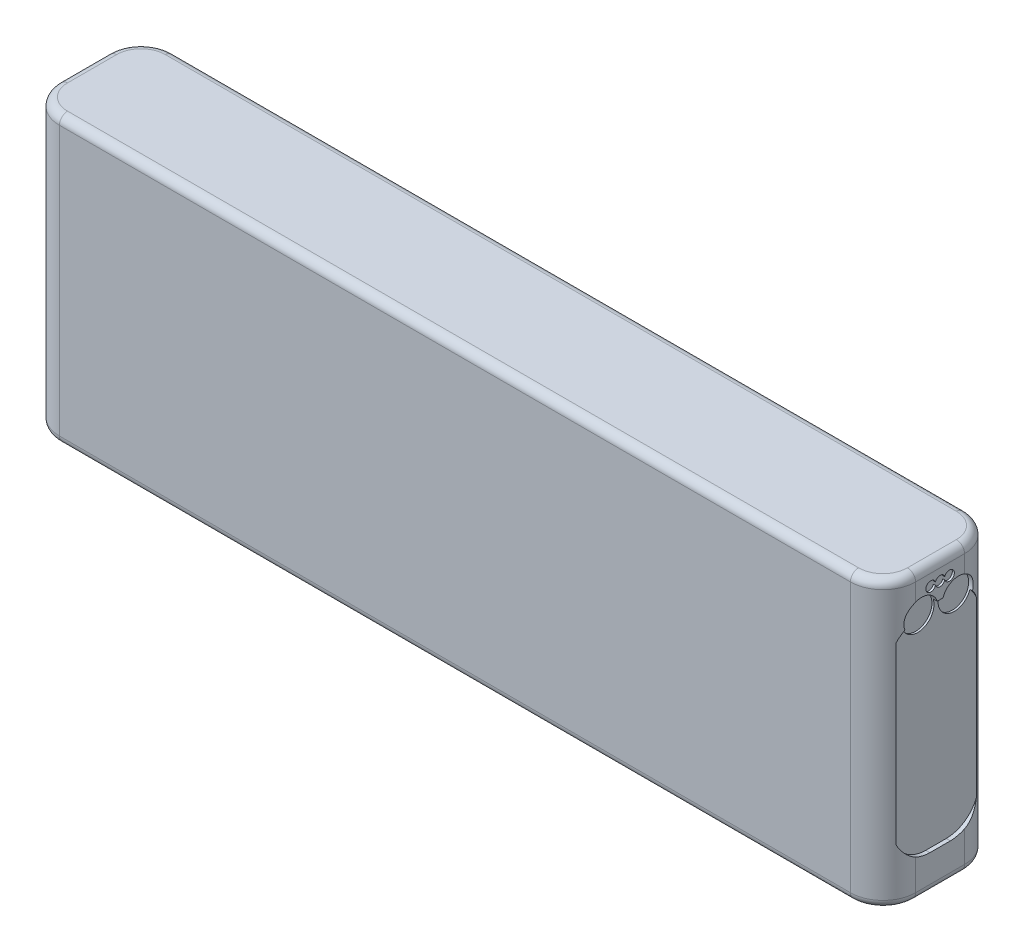
SolidWorks part; units mm, degrees
ref_plane "Front Plane" through (0, 0, 0) normal (0, 0, 1) x (1, 0, 0)
ref_plane "Top Plane" through (0, 0, 0) normal (0, 1, 0) x (1, 0, 0)
ref_plane "Right Plane" through (0, 0, 0) normal (1, 0, 0) x (0, 0, -1)
ref_plane "Plane1" through (0, 0, -15) normal (0, 0, -1) x (-1, 0, 0)
sketch "Sketch1" plane through (0, 0, -15) normal (0, 0, -1) x (-1, 0, 0)
  line L0 (-52.5, -17.5) -> (52.5, -17.5)
  line L1 (52.5, -17.5) -> (52.5, 17.5)
  line L2 (52.5, 17.5) -> (-52.5, 17.5)
  line L3 (-52.5, 17.5) -> (-52.5, -17.5)
  line L4 (-52.5, 0) -> (52.5, 0) construction
  line L5 (0, 17.5) -> (0, -17.5) construction
  dimension "D1" = 35
  dimension "D2" = 105
extrude "Boss-Extrude1" add sketch "Sketch1" against normal blind 14
sketch "Sketch2" plane through (52.5, 0, 0) normal (1, 0, 0) x (0, 0, -1)
  line L0 (2.75, 9.125) -> (2.75, -9.125)
  line L1 (6.75, -13.125) -> (9.25, -13.125)
  line L2 (13.25, -9.125) -> (13.25, 9.125)
  line L3 (9.25, 13.125) -> (6.75, 13.125)
  line L4 (1, 17.5) -> (15, -17.5) construction
  line L5 (15, 17.5) -> (1, -17.5) construction
  line L6 (2.75, 13.125) -> (13.25, -13.125) construction
  line L7 (13.25, 13.125) -> (2.75, -13.125) construction
  line L12 (1, 17.5) -> (15, 17.5) construction
  line L13 (1, 17.5) -> (1, -17.5) construction
  line L14 (1, -17.5) -> (15, -17.5) construction
  line L15 (15, 17.5) -> (15, -17.5) construction
  line L16 (1, 17.5) -> (15, -17.5) construction
  line L17 (1, -17.5) -> (15, 17.5) construction
  arc A0 (2.75, -9.125) -> (6.75, -13.125) centre (6.75, -9.125) ccw
  arc A1 (9.25, -13.125) -> (13.25, -9.125) centre (9.25, -9.125) ccw
  arc A2 (13.25, 9.125) -> (9.25, 13.125) centre (9.25, 9.125) ccw
  arc A3 (2.75, 9.125) -> (6.75, 13.125) centre (6.75, 9.125) cw
  point P16 (8, 0)
  dimension "D3" = 4
  dimension "D1" = 10.5
  dimension "D2" = 14
extrude "Cut-Extrude1" cut sketch "Sketch2" against normal blind 0.5
sketch "Sketch3" plane through (-52.5, 0, 0) normal (-1, 0, 0) x (0, 0, 1)
  line L0 (-6.75, 13.125) -> (-9.25, 13.125)
  line L1 (-13.25, 9.125) -> (-13.25, -9.125)
  line L2 (-9.25, -13.125) -> (-6.75, -13.125)
  line L3 (-2.75, -9.125) -> (-2.75, 9.125)
  line L4 (-13.25, 13.125) -> (-2.75, -13.125) construction
  line L5 (-2.75, 13.125) -> (-13.25, -13.125) construction
  line L6 (-15, 17.5) -> (-1, -17.5) construction
  line L7 (-1, -17.5) -> (-15, -17.5) construction
  line L8 (-15, -17.5) -> (-1, 17.5) construction
  arc A0 (-13.25, -9.125) -> (-9.25, -13.125) centre (-9.25, -9.125) ccw
  arc A1 (-6.75, -13.125) -> (-2.75, -9.125) centre (-6.75, -9.125) ccw
  arc A2 (-6.75, 13.125) -> (-2.75, 9.125) centre (-6.75, 9.125) cw
  arc A3 (-9.25, 13.125) -> (-13.25, 9.125) centre (-9.25, 9.125) ccw
  dimension "D3" = 4
  dimension "D1" = 10.5
  dimension "D2" = 14
extrude "Cut-Extrude2" cut sketch "Sketch3" against normal blind 0.5
fillet "Fillet1" radius 4 4 edges at (-52.5, 0, -15) (-52.5, 0, -1) (52.5, 0, -15) (52.5, 0, -1) tangent propagation no
fillet "Fillet2" radius 1 16 edges at (51.3284, 17.5, -13.8284) (52.5, 17.5, -8) (0, 17.5, -15) (51.3284, 17.5, -2.1716) (-51.3284, 17.5, -13.8284) (0, 17.5, -1) (-52.5, 17.5, -8) (-51.3284, 17.5, -2.1716) (-52.5, -17.5, -8) (-51.3284, -17.5, -13.8284) (-51.3284, -17.5, -2.1716) (0, -17.5, -15) (0, -17.5, -1) (51.3284, -17.5, -13.8284) (51.3284, -17.5, -2.1716) (52.5, -17.5, -8) tangent propagation no
sketch "Sketch4" plane through (0, 0, -1) normal (0, 0, 1) x (1, 0, 0)
  line L0 (-48.5, 0) -> (48.5, 0) construction
  line L1 (-48.5, 16.5) -> (-48.5, -16.5) construction
  line L2 (48.5, -16.5) -> (48.5, 16.5) construction
  line L3 (0, 25.9735) -> (0, -16.5) construction
  line L4 (-48.5, -16.5) -> (48.5, -16.5) construction
  circle A0 centre (0, 0) radius 0.5026
sketch "Esquisse1" plane through (52, 0, 0) normal (1, 0, 0) x (0, 0, -1)
  line L2 (5.75, 12.5) -> (10.25, 12.5) construction
  line L3 (5, 17.5) -> (11, 17.5) construction
  line L4 (5, 17.5) -> (11, 17.5) construction
  line L5 (8, 17.5) -> (8, 12.5) construction
  circle A0 centre (5.75, 12.5) radius 2
  circle A1 centre (10.25, 12.5) radius 2
  dimension "D1" = 4
  dimension "D2" = 5
  dimension "D3" = 4.5
extrude "Enlèv. mat.-Extru.1" cut sketch "Esquisse1" against normal blind 0.25 and the other way up to next
sketch "Esquisse2" plane through (52.5, 0, 0) normal (1, 0, 0) x (0, 0, -1)
  line L0 (6.85, 15.1) -> (8, 15.1) construction
  line L1 (8, 15.1) -> (9.15, 15.1) construction
  line L2 (5, 17.5) -> (11, 17.5) construction
  line L3 (5, 17.5) -> (11, 17.5) construction
  line L4 (8, 17.5) -> (8, 15.1) construction
  arc A0 (7.425, 14.9286) -> (8.575, 14.9286) centre (8, 15.1) ccw
  arc A1 (8.575, 14.9286) -> (8.575, 15.2714) centre (9.15, 15.1) ccw
  arc A2 (7.425, 15.2714) -> (7.425, 14.9286) centre (6.85, 15.1) ccw
  arc A3 (8.575, 15.2714) -> (7.425, 15.2714) centre (8, 15.1) ccw
  dimension "D1" = 1.2
  dimension "D2" = 2.4
  dimension "D3" = 1.15
  dimension "D4" = 1.15
extrude "Enlèv. mat.-Extru.4" cut sketch "Esquisse2" against normal blind 0.25
equation "\"D1@Sketch3\"=\"D2@Sketch3\" * .75"
equation "\"D1@Sketch2\"=\"D2@Sketch2\"* .75"
